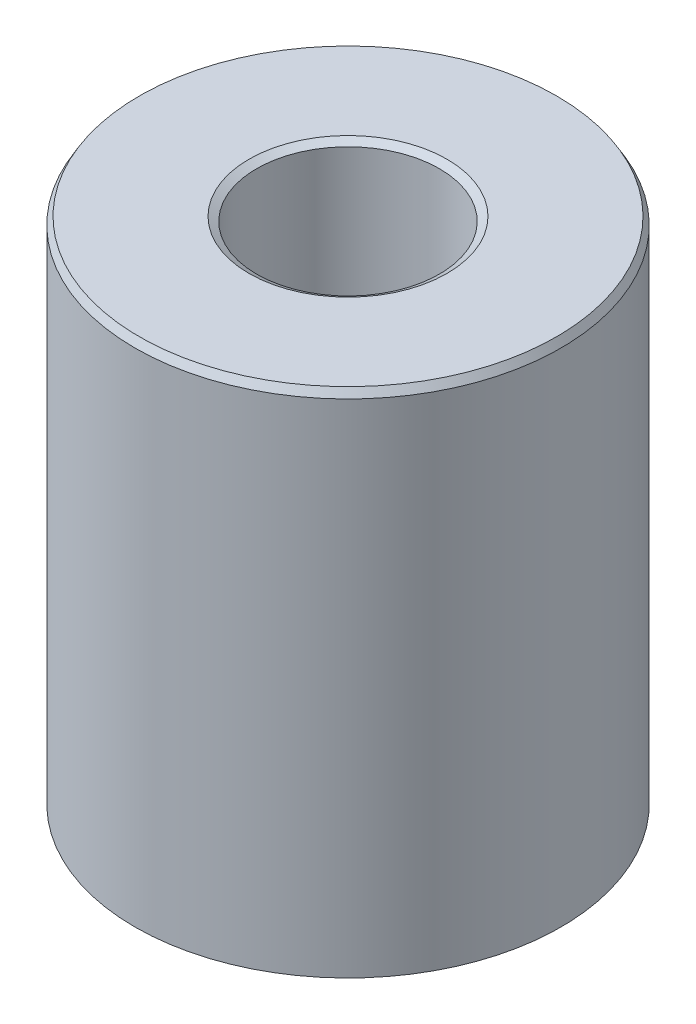
SolidWorks part; units mm, degrees
ref_plane "Front Plane" through (0, 0, 0) normal (0, 0, 1) x (1, 0, 0)
ref_plane "Top Plane" through (0, 0, 0) normal (0, 1, 0) x (1, 0, 0)
ref_plane "Right Plane" through (0, 0, 0) normal (1, 0, 0) x (0, 0, -1)
sketch "Sketch1" plane through (0, 0, 0) normal (0, 1, 0) x (1, 0, 0)
  circle A0 centre (0, 0) radius 35
  dimension "SLEEVE_OD" = 70
extrude "Boss-Extrude1" add sketch "Sketch1" along normal blind 84.369
sketch "Sketch2" plane through (0, 0, 0) normal (0, 1, 0) x (1, 0, 0)
  circle A0 centre (0, 0) radius 15.0197
  dimension "BORE_D" = 30.0394
extrude "Cut-Extrude1" cut sketch "Sketch2" along normal through all
chamfer "Chamfer1" distance 1.2476 angle 30 4 edges at (0, 84.369, 15.0197) (0, 0, 15.0197) (0, 0, 35) (0, 84.369, 35) first distance on face at (0, 84.369, 15.0197) first distance on face at (0, 0, 15.0197) first distance on face at (0, 84.369, 35)
